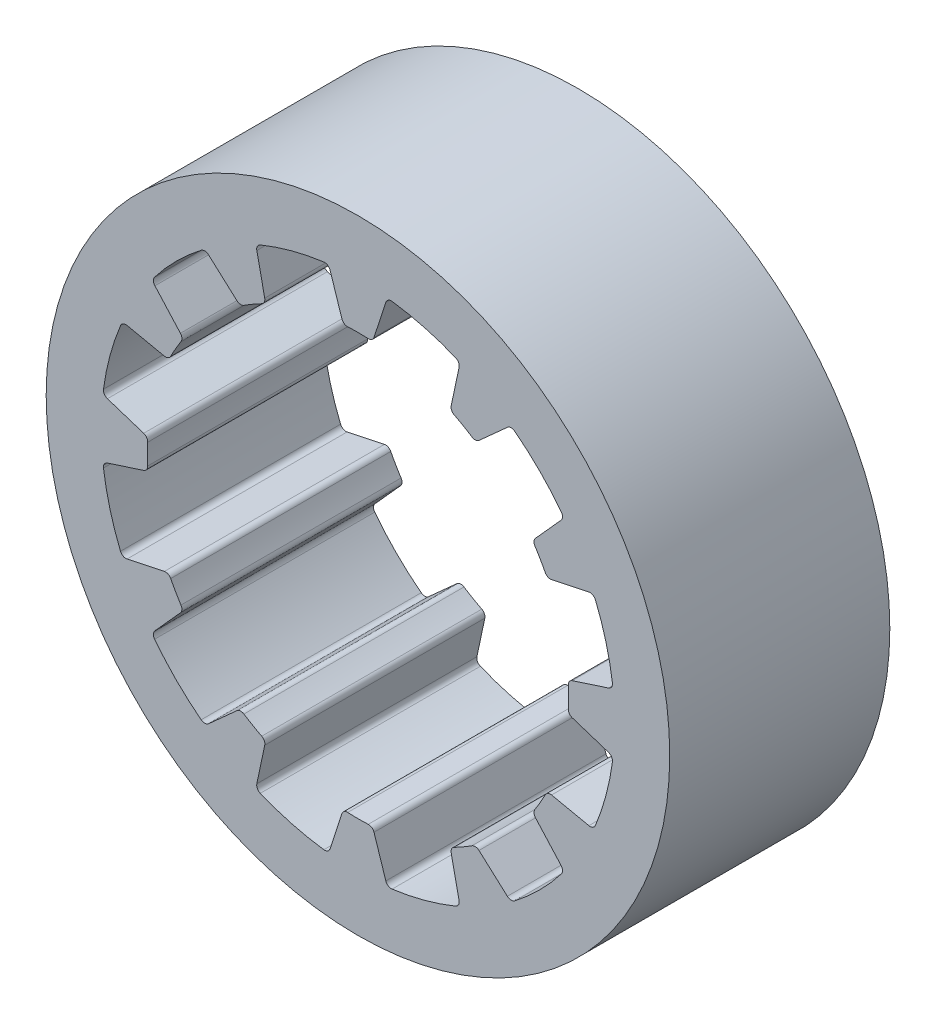
SolidWorks part; units mm, degrees
ref_plane "Front Plane" through (0, 0, 0) normal (0, 0, 1) x (1, 0, 0)
ref_plane "Top Plane" through (0, 0, 0) normal (0, 1, 0) x (1, 0, 0)
ref_plane "Right Plane" through (0, 0, 0) normal (1, 0, 0) x (0, 0, -1)
sketch "Model" plane through (0, 0, 0) normal (0, 0, 1) x (1, 0, 0)
  line L0 (-8.0705, 16.7577) -> (-8.7545, 19.9877)
  line L1 (-12.9326, 17.5755) -> (-10.4773, 15.3681)
  line L2 (-15.3681, 10.4773) -> (-17.5755, 12.9326)
  line L3 (-19.9877, 8.7545) -> (-16.7577, 8.0705)
  line L4 (-18.5478, 1.3896) -> (-21.6871, 2.4122)
  line L5 (-21.6871, -2.4122) -> (-18.5478, -1.3896)
  line L6 (-16.7577, -8.0705) -> (-19.9877, -8.7545)
  line L7 (-17.5755, -12.9326) -> (-15.3681, -10.4773)
  line L8 (-10.4773, -15.3681) -> (-12.9326, -17.5755)
  line L9 (-8.7545, -19.9877) -> (-8.0705, -16.7577)
  line L10 (-1.3896, -18.5478) -> (-2.4122, -21.6871)
  line L11 (2.4122, -21.6871) -> (1.3896, -18.5478)
  line L12 (8.0705, -16.7577) -> (8.7545, -19.9877)
  line L13 (12.9326, -17.5755) -> (10.4773, -15.3681)
  line L14 (15.3681, -10.4773) -> (17.5755, -12.9326)
  line L15 (19.9877, -8.7545) -> (16.7577, -8.0705)
  line L16 (18.5478, -1.3896) -> (21.6871, -2.4122)
  line L17 (21.6871, 2.4122) -> (18.5478, 1.3896)
  line L18 (16.7577, 8.0705) -> (19.9877, 8.7545)
  line L19 (17.5755, 12.9326) -> (15.3681, 10.4773)
  line L20 (10.4773, 15.3681) -> (12.9326, 17.5755)
  line L21 (8.7545, 19.9877) -> (8.0705, 16.7577)
  line L22 (1.3896, 18.5478) -> (2.4122, 21.6871)
  line L23 (-2.4122, 21.6871) -> (-1.3896, 18.5478)
  arc A0 (-2.9541, 22.0278) -> (-8.4556, 20.5537) centre (0, 0) ccw
  arc A1 (-8.4556, 20.5537) -> (-8.7545, 19.9877) centre (-8.2654, 20.0913) ccw
  arc A2 (-8.3311, 16.2094) -> (-8.0705, 16.7577) centre (-8.5596, 16.6541) ccw
  arc A3 (-8.3311, 16.2094) -> (-9.8722, 15.3196) centre (0, 0) ccw
  arc A4 (-10.4773, 15.3681) -> (-9.8722, 15.3196) centre (-10.143, 15.7399) ccw
  arc A5 (-12.9326, 17.5755) -> (-13.5722, 17.5996) centre (-13.2669, 17.2037) ccw
  arc A6 (-13.5722, 17.5996) -> (-17.5996, 13.5722) centre (0, 0) ccw
  arc A7 (-17.5996, 13.5722) -> (-17.5755, 12.9326) centre (-17.2037, 13.2669) ccw
  arc A8 (-15.3196, 9.8722) -> (-15.3681, 10.4773) centre (-15.7399, 10.143) ccw
  arc A9 (-15.3196, 9.8722) -> (-16.2094, 8.3311) centre (0, 0) ccw
  arc A10 (-16.7577, 8.0705) -> (-16.2094, 8.3311) centre (-16.6541, 8.5596) ccw
  arc A11 (-19.9877, 8.7545) -> (-20.5537, 8.4556) centre (-20.0913, 8.2654) ccw
  arc A12 (-20.5537, 8.4556) -> (-22.0278, 2.9541) centre (0, 0) ccw
  arc A13 (-22.0278, 2.9541) -> (-21.6871, 2.4122) centre (-21.5322, 2.8876) ccw
  arc A14 (-18.2033, 0.8898) -> (-18.5478, 1.3896) centre (-18.7027, 0.9142) ccw
  arc A15 (-18.2033, 0.8898) -> (-18.2033, -0.8898) centre (0, 0) ccw
  arc A16 (-18.5478, -1.3896) -> (-18.2033, -0.8898) centre (-18.7027, -0.9142) ccw
  arc A17 (-21.6871, -2.4122) -> (-22.0278, -2.9541) centre (-21.5322, -2.8876) ccw
  arc A18 (-22.0278, -2.9541) -> (-20.5537, -8.4556) centre (0, 0) ccw
  arc A19 (-20.5537, -8.4556) -> (-19.9877, -8.7545) centre (-20.0913, -8.2654) ccw
  arc A20 (-16.2094, -8.3311) -> (-16.7577, -8.0705) centre (-16.6541, -8.5596) ccw
  arc A21 (-16.2094, -8.3311) -> (-15.3196, -9.8722) centre (0, 0) ccw
  arc A22 (-15.3681, -10.4773) -> (-15.3196, -9.8722) centre (-15.7399, -10.143) ccw
  arc A23 (-17.5755, -12.9326) -> (-17.5996, -13.5722) centre (-17.2037, -13.2669) ccw
  arc A24 (-17.5996, -13.5722) -> (-13.5722, -17.5996) centre (0, 0) ccw
  arc A25 (-13.5722, -17.5996) -> (-12.9326, -17.5755) centre (-13.2669, -17.2037) ccw
  arc A26 (-9.8722, -15.3196) -> (-10.4773, -15.3681) centre (-10.143, -15.7399) ccw
  arc A27 (-9.8722, -15.3196) -> (-8.3311, -16.2094) centre (0, 0) ccw
  arc A28 (-8.0705, -16.7577) -> (-8.3311, -16.2094) centre (-8.5596, -16.6541) ccw
  arc A29 (-8.7545, -19.9877) -> (-8.4556, -20.5537) centre (-8.2654, -20.0913) ccw
  arc A30 (-8.4556, -20.5537) -> (-2.9541, -22.0278) centre (0, 0) ccw
  arc A31 (-2.9541, -22.0278) -> (-2.4122, -21.6871) centre (-2.8876, -21.5322) ccw
  arc A32 (-0.8898, -18.2033) -> (-1.3896, -18.5478) centre (-0.9142, -18.7027) ccw
  arc A33 (-0.8898, -18.2033) -> (0.8898, -18.2033) centre (0, 0) ccw
  arc A34 (1.3896, -18.5478) -> (0.8898, -18.2033) centre (0.9142, -18.7027) ccw
  arc A35 (2.4122, -21.6871) -> (2.9541, -22.0278) centre (2.8876, -21.5322) ccw
  arc A36 (2.9541, -22.0278) -> (8.4556, -20.5537) centre (0, 0) ccw
  arc A37 (8.4556, -20.5537) -> (8.7545, -19.9877) centre (8.2654, -20.0913) ccw
  arc A38 (8.3311, -16.2094) -> (8.0705, -16.7577) centre (8.5596, -16.6541) ccw
  arc A39 (8.3311, -16.2094) -> (9.8722, -15.3196) centre (0, 0) ccw
  arc A40 (10.4773, -15.3681) -> (9.8722, -15.3196) centre (10.143, -15.7399) ccw
  arc A41 (12.9326, -17.5755) -> (13.5722, -17.5996) centre (13.2669, -17.2037) ccw
  arc A42 (13.5722, -17.5996) -> (17.5996, -13.5722) centre (0, 0) ccw
  arc A43 (17.5996, -13.5722) -> (17.5755, -12.9326) centre (17.2037, -13.2669) ccw
  arc A44 (15.3196, -9.8722) -> (15.3681, -10.4773) centre (15.7399, -10.143) ccw
  arc A45 (15.3196, -9.8722) -> (16.2094, -8.3311) centre (0, 0) ccw
  arc A46 (16.7577, -8.0705) -> (16.2094, -8.3311) centre (16.6541, -8.5596) ccw
  arc A47 (19.9877, -8.7545) -> (20.5537, -8.4556) centre (20.0913, -8.2654) ccw
  arc A48 (20.5537, -8.4556) -> (22.0278, -2.9541) centre (0, 0) ccw
  arc A49 (22.0278, -2.9541) -> (21.6871, -2.4122) centre (21.5322, -2.8876) ccw
  arc A50 (18.2033, -0.8898) -> (18.5478, -1.3896) centre (18.7027, -0.9142) ccw
  arc A51 (18.2033, -0.8898) -> (18.2033, 0.8898) centre (0, 0) ccw
  arc A52 (18.5478, 1.3896) -> (18.2033, 0.8898) centre (18.7027, 0.9142) ccw
  arc A53 (21.6871, 2.4122) -> (22.0278, 2.9541) centre (21.5322, 2.8876) ccw
  arc A54 (22.0278, 2.9541) -> (20.5537, 8.4556) centre (0, 0) ccw
  arc A55 (20.5537, 8.4556) -> (19.9877, 8.7545) centre (20.0913, 8.2654) ccw
  arc A56 (16.2094, 8.3311) -> (16.7577, 8.0705) centre (16.6541, 8.5596) ccw
  arc A57 (16.2094, 8.3311) -> (15.3196, 9.8722) centre (0, 0) ccw
  arc A58 (15.3681, 10.4773) -> (15.3196, 9.8722) centre (15.7399, 10.143) ccw
  arc A59 (17.5755, 12.9326) -> (17.5996, 13.5722) centre (17.2037, 13.2669) ccw
  arc A60 (17.5996, 13.5722) -> (13.5722, 17.5996) centre (0, 0) ccw
  arc A61 (13.5722, 17.5996) -> (12.9326, 17.5755) centre (13.2669, 17.2037) ccw
  arc A62 (9.8722, 15.3196) -> (10.4773, 15.3681) centre (10.143, 15.7399) ccw
  arc A63 (9.8722, 15.3196) -> (8.3311, 16.2094) centre (0, 0) ccw
  arc A64 (8.0705, 16.7577) -> (8.3311, 16.2094) centre (8.5596, 16.6541) ccw
  arc A65 (8.7545, 19.9877) -> (8.4556, 20.5537) centre (8.2654, 20.0913) ccw
  arc A66 (8.4556, 20.5537) -> (2.9541, 22.0278) centre (0, 0) ccw
  arc A67 (2.9541, 22.0278) -> (2.4122, 21.6871) centre (2.8876, 21.5322) ccw
  arc A68 (0.8898, 18.2033) -> (1.3896, 18.5478) centre (0.9142, 18.7027) ccw
  arc A69 (0.8898, 18.2033) -> (-0.8898, 18.2033) centre (0, 0) ccw
  arc A70 (-1.3896, 18.5478) -> (-0.8898, 18.2033) centre (-0.9142, 18.7027) ccw
  arc A71 (-2.4122, 21.6871) -> (-2.9541, 22.0278) centre (-2.8876, 21.5322) ccw
  circle A72 centre (0, 0) radius 10
  circle A73 centre (0, 0) radius 26.9875
  dimension "D3" = 53.975
  dimension "D1" = 0
  dimension "D2" = 0
extrude "Boss-Extrude1" add sketch "Model" along normal blind 19.05 contours A73 A71 L23 A70 A69 A68 L22 A67 A66 A65 L21 A64 A63 A62 L20 A61 A60 A59 L19 A58 A57 A56 L18 A55 A54 A53 L17 A52 A51 A50 L16 A49 A48 A47 L15 A46 A45 A44 L14 A43 A42 A41 L13 A40 A39 A38 L12 A37 A36 A35 region at (-26.2242, 0, 0)
